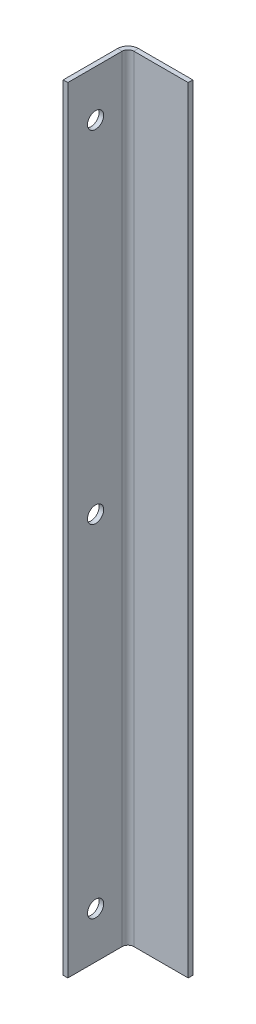
SolidWorks part; units mm, degrees
note: The reader was unsure of these and kept them because the rebuilt part matched: flange length of "Edge-Flange1".
material "AISI 304"
ref_plane "Front" through (0, 0, 0) normal (0, 0, 1) x (1, 0, 0)
ref_plane "Top" through (0, 0, 0) normal (0, 1, 0) x (1, 0, 0)
ref_plane "Right" through (0, 0, 0) normal (1, 0, 0) x (0, 0, -1)
sketch "Sketch1" plane through (0, 0, 0) normal (1, 0, 0) x (0, 0, -1)
  line L1 (-14, -167.5) -> (14, -167.5)
  line L2 (-14, -167.5) -> (-14, 167.5)
  line L3 (-14, 167.5) -> (14, 167.5)
  line L4 (14, -167.5) -> (14, 167.5)
  line L5 (-14, -167.5) -> (14, 167.5) construction
  line L6 (-14, 167.5) -> (14, -167.5) construction
  point P0 (0, 0)
  dimension "D1" = 28
  dimension "D2" = 335
base flange "Base-Flange1" sketch "Sketch1" thickness 2 reverse thickness direction no parameters "D1"=8
edge flange "Edge-Flange1" sketch "Sketch8" flange angle 90 flange length 28 flange position material inside bend radius 2.5 thickness 2 relief rectangular parameters "D6"=10, "D8"=1
sketch "Sketch8" plane through (0, 0, -14) normal (0, 0, -1) x (0, 1, 0)
  line L2 (-167.5, 0) -> (-167.5, 26)
  line L3 (-167.5, 26) -> (167.5, 26)
  line L4 (167.5, 26) -> (167.5, 0)
  line L7 (-167.5, 0) -> (167.5, 0) construction
  line L8 (-167.5, 0) -> (167.5, 0)
bend "EdgeBend1" bend radius 2.5 bend angle 90 parameters "D5"=1
sketch "Sketch9" plane through (0, 0, 0) normal (1, 0, 0) x (0, 0, -1)
  line L0 (-14, 167.5) -> (-14, -167.5) construction
  line L1 (9.5, 167.5) -> (-14, 167.5) construction
  circle A0 centre (-2, 147.5) radius 3.5
  dimension "D1" = 7
  dimension "D2" = 12
  dimension "D3" = 20
extrude "Cut-Extrude1" cut sketch "Sketch9" against normal blind 10 normal cut yes
mirror "Mirror1" about plane through (0, 0, 0) normal (0, 1, 0) of "Cut-Extrude1"
pattern_linear "LPattern1" count 2 spacing 147.5 along (0, -1, 0) of "Cut-Extrude1"
sketch "Bend-Lines1" [suppressed] plane through (0, 0, 0) normal (0, 1, 0) x (1, 0, 0)
sketch "Bounding-Box1" [suppressed] plane through (0, 0, 0) normal (0, 1, 0) x (1, 0, 0)
sheet metal parameters "Sheet-Metal1" thickness 2 parameters "D1"=8
flat pattern "Flat-Pattern1" [suppressed]
sketch "Bend-Lines2" plane through (0, 0, 0) normal (0, 1, 0) x (1, 0, 0)
sketch3d "Bounding-Box2" [suppressed]
  line L0 (15, 191, 0) -> (15, -191, 0) construction
  line L1 (-15, 191, 0) -> (-15, -191, 0) construction
  line L2 (15, 191, 0) -> (-15, 191, 0) construction
  line L3 (15, -191, 0) -> (-15, -191, 0) construction
sheet metal parameters "Sheet-Metal2" thickness 2 parameters "D1"=8
flat pattern "Flat-Pattern1"
sketch "Bend-Lines2" plane through (0, 0, 0) normal (1, 0, 0) x (0, 0, -1)
  line L0 (12.2489, -167.5) -> (12.2489, 167.5) construction
  line L1 (12.2489, -167.5) -> (12.2489, 167.5) construction
sketch3d "Bounding-Box2" [suppressed]
  line L0 (-14, 167.5, 0) -> (-14, -167.5, 0) construction
  line L1 (38.4978, 167.5, 0) -> (38.4978, -167.5, 0) construction
  line L2 (-14, 167.5, 0) -> (38.4978, 167.5, 0) construction
  line L3 (-14, -167.5, 0) -> (38.4978, -167.5, 0) construction
bend of the flat pattern "Flatten-<EdgeBend1>1"
sheet metal parameters "Sheet-Metal3" thickness 2 parameters "D1"=8
flat pattern "Flat-Pattern1"
sketch "Bend-Lines2" plane through (0, 0, 0) normal (1, 0, 0) x (0, 0, -1)
  line L0 (12.2489, -167.5) -> (12.2489, 167.5) construction
  line L1 (12.2489, -167.5) -> (12.2489, 167.5) construction
sketch3d "Bounding-Box2" [suppressed]
  line L0 (-14, 167.5, 0) -> (-14, -167.5, 0) construction
  line L1 (38.4978, 167.5, 0) -> (38.4978, -167.5, 0) construction
  line L2 (-14, 167.5, 0) -> (38.4978, 167.5, 0) construction
  line L3 (-14, -167.5, 0) -> (38.4978, -167.5, 0) construction
bend of the flat pattern "Flatten-<EdgeBend1>1"
sheet metal parameters "Sheet-Metal4" thickness 2 parameters "D1"=8
flat pattern "Flat-Pattern1"
sketch "Bend-Lines2" plane through (0, 0, 0) normal (1, 0, 0) x (0, 0, -1)
  line L0 (12.2489, -167.5) -> (12.2489, 167.5) construction
  line L1 (12.2489, -167.5) -> (12.2489, 167.5) construction
sketch3d "Bounding-Box2" [suppressed]
  line L0 (-14, 167.5, 0) -> (-14, -167.5, 0) construction
  line L1 (38.4978, 167.5, 0) -> (38.4978, -167.5, 0) construction
  line L2 (-14, 167.5, 0) -> (38.4978, 167.5, 0) construction
  line L3 (-14, -167.5, 0) -> (38.4978, -167.5, 0) construction
bend of the flat pattern "Flatten-<EdgeBend1>1"
sheet metal parameters "Sheet-Metal5" thickness 2 parameters "D1"=8
flat pattern "Flat-Pattern1"
sketch "Bend-Lines2" plane through (0, 0, 0) normal (1, 0, 0) x (0, 0, -1)
  line L0 (12.2489, -167.5) -> (12.2489, 167.5) construction
  line L1 (12.2489, -167.5) -> (12.2489, 167.5) construction
sketch3d "Bounding-Box2" [suppressed]
  line L0 (-14, 167.5, 0) -> (-14, -167.5, 0) construction
  line L1 (38.4978, 167.5, 0) -> (38.4978, -167.5, 0) construction
  line L2 (-14, 167.5, 0) -> (38.4978, 167.5, 0) construction
  line L3 (-14, -167.5, 0) -> (38.4978, -167.5, 0) construction
bend of the flat pattern "Flatten-<EdgeBend1>1"
